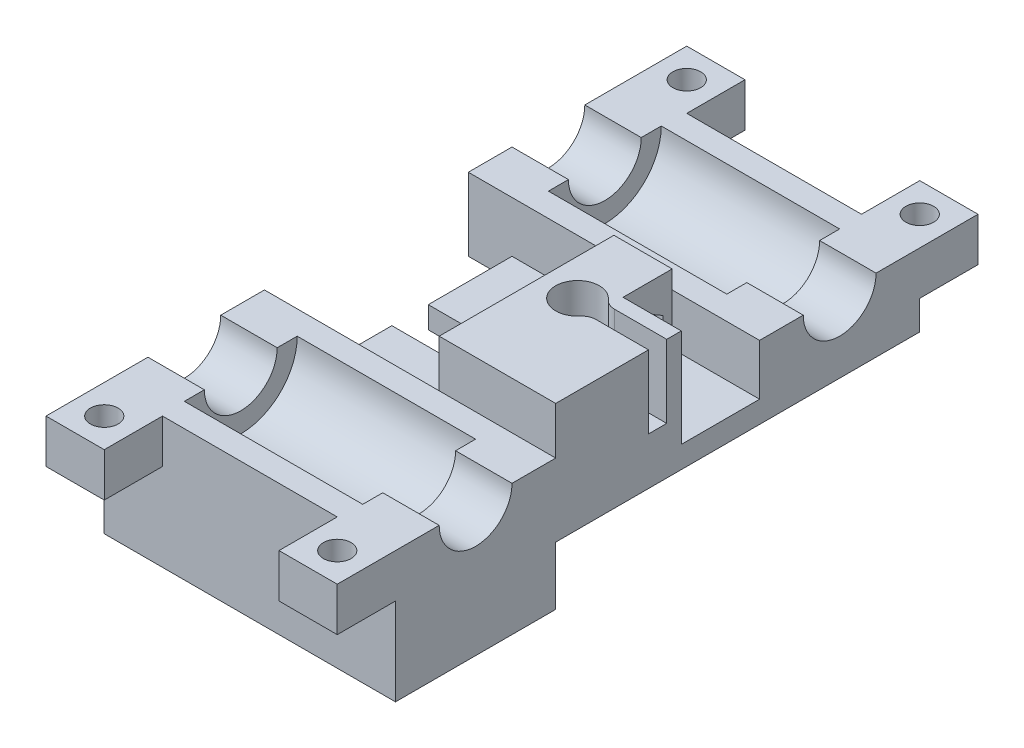
SolidWorks part; units mm, degrees
ref_plane "Front Plane" through (0, 0, 0) normal (0, 0, 1) x (1, 0, 0)
ref_plane "Top Plane" through (0, 0, 0) normal (0, 1, 0) x (1, 0, 0)
ref_plane "Right Plane" through (0, 0, 0) normal (1, 0, 0) x (0, 0, -1)
sketch "Sketch1" plane through (0, 0, 0) normal (0, 1, 0) x (1, 0, 0)
  line L1 (-20, 11) -> (20, 11)
  line L2 (-20, 11) -> (-20, -11)
  line L3 (-20, -11) -> (20, -11)
  line L4 (20, 11) -> (20, -11)
  line L5 (-20, 11) -> (20, -11) construction
  line L6 (-20, -11) -> (20, 11) construction
  point P0 (0, 0)
  dimension "D1" = 40
  dimension "D2" = 22
extrude "Boss-Extrude1" add sketch "Sketch1" along normal blind 11
sketch "Sketch2" plane through (0, 0, 0) normal (0, 1, 0) x (1, 0, 0)
  line L4 (20, -11) -> (20, 11)
  line L5 (-20, -11) -> (20, -11)
  line L6 (-20, 11) -> (-20, -11)
  line L7 (20, 11) -> (-20, 11)
  line L8 (20, -11) -> (20, 11)
  line L9 (-20, -11) -> (20, -11)
  line L10 (-20, 11) -> (-20, -11)
  line L11 (20, 11) -> (-20, 11)
  circle A0 centre (0, 0) radius 4
  dimension "D2" = 8
  dimension "D1" = 0
extrude "Boss-Extrude2" add sketch "Sketch2" against normal blind 7
sketch "Sketch3" plane through (0, 11, 0) normal (0, 1, 0) x (1, 0, 0)
  line L1 (12.25, -7.75) -> (-12.25, -7.75)
  line L2 (12.25, -7.75) -> (12.25, 7.75)
  line L3 (12.25, 7.75) -> (-12.25, 7.75)
  line L4 (-12.25, -7.75) -> (-12.25, 7.75)
  line L5 (12.25, -7.75) -> (-12.25, 7.75) construction
  line L6 (12.25, 7.75) -> (-12.25, -7.75) construction
  point P0 (0, 0)
  dimension "D1" = 15.5
  dimension "D2" = 24.5
extrude "Cut-Extrude1" cut sketch "Sketch3" against normal blind 7.75
fillet "Fillet1" radius 7.75 2 edges at (0, 3.25, 7.75) (0, 3.25, -7.75)
sketch "Sketch4" plane through (-12.25, 0, 0) normal (1, 0, 0) x (0, 0, -1)
  line L0 (7.75, 11) -> (-7.75, 11) construction
  circle A0 centre (0, 11) radius 5
  dimension "D1" = 10
extrude "Cut-Extrude2" cut sketch "Sketch4" against normal through all both and the other way through all
sketch "Sketch5" plane through (0, 11, 0) normal (0, 1, 0) x (1, 0, 0)
  line L1 (20, -11) -> (12, -11)
  line L2 (20, -11) -> (20, -19)
  line L3 (20, -19) -> (12, -19)
  line L4 (12, -11) -> (12, -19)
  circle A0 centre (16, -15) radius 1.9058
  dimension "D1" = 8
  dimension "D2" = 8
  dimension "D3" = 4
  dimension "D4" = 4
extrude "Boss-Extrude3" add sketch "Sketch5" against normal blind 6
sketch "Sketch6" plane through (0, 5, 0) normal (0, -1, 0) x (1, 0, 0)
  line L4 (20, 11) -> (20, 19)
  line L5 (20, 19) -> (12, 19)
  line L6 (12, 19) -> (12, 11)
  line L7 (12, 11) -> (20, 11)
  line L8 (20, 11) -> (20, 19)
  line L9 (20, 19) -> (12, 19)
  line L10 (12, 19) -> (12, 11)
  line L11 (12, 11) -> (20, 11)
  circle A0 centre (16, 15) radius 1.9058 construction
  circle A1 centre (16, 15) radius 1.9058
  circle A2 centre (16, 15) radius 3
  circle M6 centre (16, 15) radius 1.9058
  dimension "D2" = 6
  dimension "D1" = 0
extrude "Cut-Extrude3" cut sketch "Sketch6" against normal blind 3 contours A2 M6 region at (13.0849, 5, 15)
mirror "Mirror8" about plane through (0, 0, 0) normal (1, 0, 0) of "Cut-Extrude3", "Boss-Extrude3"
mirror "Mirror9" [suppressed] about plane through (0, 0, 0) normal (0, 0, 1)
chamfer "Chamfer2" [suppressed] distance 4 angle 45
ref_plane "Plane1" through (0, 0, -25) normal (0, 0, 1) x (1, 0, 0)
sketch "Sketch7" plane through (0, 0, -11) normal (0, 0, -1) x (-1, 0, 0)
  line L0 (-20, 11) -> (-20, -7) construction
  line L1 (-20, 1) -> (-4, 1)
  line L2 (-20, 1) -> (-20, 17.5)
  line L3 (-20, 17.5) -> (-4, 17.5)
  line L4 (-4, 1) -> (-4, 17.5)
  line L5 (-20, 11) -> (20, 11) construction
  dimension "D1" = 16
  dimension "D2" = 16.5
  dimension "D3" = 6.5
extrude "Boss-Extrude5" add sketch "Sketch7" along normal blind 28
mirror "Mirror14" about plane through (0, 0, -25) normal (0, 0, 1) of "Mirror8", "Cut-Extrude3", "Boss-Extrude3", "Cut-Extrude2", "Fillet1", "Cut-Extrude1", "Boss-Extrude2", "Boss-Extrude1"
sketch "Sketch9" plane through (4, 0, 0) normal (-1, 0, 0) x (0, 0, 1)
  line L0 (-39, 1) -> (-39, 11) construction
  line L1 (-11, 1) -> (-39, 1)
  line L2 (-11, 1) -> (-11, 4)
  line L3 (-11, 4) -> (-39, 4)
  line L4 (-39, 1) -> (-39, 4)
  dimension "D1" = 3
extrude "Boss-Extrude6" add sketch "Sketch9" along normal blind 18
sketch "Sketch10" plane through (0, 17.5, 0) normal (0, 1, 0) x (1, 0, 0)
  line L0 (-12.375, 25) -> (12.375, 25) construction
  line L1 (20, 39) -> (20, 11) construction
  line L3 (9, 23.75) -> (20, 23.75)
  line L4 (9, 23.75) -> (9, 26.25)
  line L5 (9, 26.25) -> (20, 26.25)
  line L6 (20, 23.75) -> (20, 26.25)
  circle A0 centre (9, 25) radius 3
  line M4 (20, 11) -> (20, 39)
  dimension "D3" = 6
  dimension "D1" = 0
  dimension "D2" = 11
  dimension "D4" = 2.5
  dimension "D5" = 1.25
extrude "Cut-Extrude4" cut sketch "Sketch10" against normal blind 10 contours L3 A0 L5 L4 | L5 A0 L3 L4 | A0 L3 L5 M4 region at (10.4565, 17.5, -25) region at (8.4952, 17.5, -25) region at (15.955, 17.5, -25)
sketch "Sketch11" plane through (0, 7.5, 0) normal (0, 1, 0) x (1, 0, 0)
  arc A0 (11.7272, 26.25) -> (11.7272, 23.75) centre (9, 25) ccw construction
  arc A1 (11.7272, 26.25) -> (11.7272, 23.75) centre (9, 25) ccw
  circle A2 centre (9, 25) radius 1.75
  dimension "D1" = 3.5
extrude "Cut-Extrude5" cut sketch "Sketch11" against normal through all both and the other way through all contours A2 region at (9, 7.5, -25)
sketch "Sketch12" plane through (4, 0, 0) normal (-1, 0, 0) x (0, 0, 1)
  line L1 (-39, 4) -> (-39, 11) construction
  circle A0 centre (-31, 11) radius 1.75
  dimension "D3" = 3.5
  dimension "D1" = 0
  dimension "D2" = 8
extrude "Cut-Extrude6" cut sketch "Sketch12" against normal through all both and the other way through all
sketch "Sketch15" plane through (20, 0, 0) normal (1, 0, 0) x (0, 0, -1)
  line L1 (32.6923, 13.6869) -> (29.5192, 13.809)
  line L2 (29.5192, 13.809) -> (27.8269, 11.1221)
  line L3 (27.8269, 11.1221) -> (29.3077, 8.3131)
  line L4 (29.3077, 8.3131) -> (32.4808, 8.191)
  line L5 (32.4808, 8.191) -> (34.1731, 10.8779)
  line L6 (34.1731, 10.8779) -> (32.6923, 13.6869)
  circle A0 centre (31, 11) radius 1.75 construction
  circle A1 centre (31, 11) radius 1.75
  circle A2 centre (31, 11) radius 2.75 construction
  dimension "D1" = 5.5
extrude "Cut-Extrude9" [suppressed] cut sketch "Sketch15" against normal blind 12 contours L1 L2 L3 L4 L5 L6
sketch "Sketch16" [suppressed] plane through (20, 0, 0) normal (1, 0, 0) x (0, 0, -1)
  line L1 (27, 11) -> (39, 11)
  line L2 (27, 11) -> (27, 17.5)
  line L3 (27, 17.5) -> (39, 17.5)
  line L4 (39, 11) -> (39, 17.5)
  circle A0 centre (31, 11) radius 1.75 construction
  circle A1 centre (31, 11) radius 1.75
  circle A2 centre (31, 11) radius 4
  dimension "D1" = 8
extrude "Cut-Extrude11" [suppressed] cut sketch "Sketch16" against normal blind 8
chamfer "Chamfer3" [suppressed] distance 2.5 angle 45
fillet "Fillet2" radius 2 2 edges at (11.7272, 12.5, -23.75) (11.7272, 12.5, -26.25)
sketch "Sketch17" plane through (0, 1, 0) normal (0, -1, 0) x (1, 0, 0)
  line L1 (12.1754, -25) -> (10.5877, -22.25)
  line L2 (10.5877, -22.25) -> (7.4123, -22.25)
  line L3 (7.4123, -22.25) -> (5.8246, -25)
  line L4 (5.8246, -25) -> (7.4123, -27.75)
  line L5 (7.4123, -27.75) -> (10.5877, -27.75)
  line L6 (10.5877, -27.75) -> (12.1754, -25)
  circle A0 centre (9, -25) radius 1.75 construction
  circle A1 centre (9, -25) radius 1.75
  circle A2 centre (9, -25) radius 2.75 construction
  dimension "D1" = 5.5
extrude "Cut-Extrude12" cut sketch "Sketch17" against normal blind 3
sketch "Sketch18" plane through (0, 4, 0) normal (0, 1, 0) x (1, 0, 0)
  line L0 (-14, 11) -> (-14, 39) construction
  line L1 (-14, 22.5) -> (4, 22.5)
  line L2 (-14, 22.5) -> (-14, 27.5)
  line L3 (-14, 27.5) -> (4, 27.5)
  line L4 (4, 22.5) -> (4, 27.5)
  line L5 (-12.375, 25) -> (12.375, 25) construction
  dimension "D1" = 2.5
  dimension "D2" = 5
  dimension "D3" = 18
extrude "Cut-Extrude13" cut sketch "Sketch18" against normal through all both and the other way through all
fillet "Fillet3" radius 2.5 2 edges at (4, 2.5, -27.5) (4, 2.5, -22.5)
sketch "Sketch19" plane through (0, 1, 0) normal (0, -1, 0) x (1, 0, 0)
  line L4 (20, -39) -> (-20, -39)
  line L5 (-20, -39) -> (-20, -61)
  line L6 (-20, -61) -> (20, -61)
  line L7 (-14, -22.5) -> (1.5, -22.5)
  line L8 (1.5, -27.5) -> (-14, -27.5)
  line L9 (-14, -27.5) -> (-14, -39)
  line L10 (-14, -39) -> (20, -39)
  line L11 (20, -39) -> (20, -11)
  line L12 (20, -11) -> (-14, -11)
  line L13 (-14, -11) -> (-14, -22.5)
  line L14 (-14, -22.5) -> (1.5, -22.5)
  line L15 (1.5, -27.5) -> (-14, -27.5)
  line L16 (-14, -27.5) -> (-14, -39)
  line L17 (-14, -39) -> (20, -39)
  line L18 (20, -39) -> (20, -11)
  line L19 (20, -11) -> (-14, -11)
  line L20 (-14, -11) -> (-14, -22.5)
  line L21 (20, -61) -> (20, -39)
  line L22 (20, -39) -> (-20, -39)
  line L23 (-20, -39) -> (-20, -61)
  line L24 (-20, -61) -> (20, -61)
  line L25 (20, -61) -> (20, -39)
  arc A2 (4, -25) -> (1.5, -22.5) centre (1.5, -25) ccw
  arc A3 (1.5, -27.5) -> (4, -25) centre (1.5, -25) ccw
  arc A4 (4, -25) -> (1.5, -22.5) centre (1.5, -25) ccw
  arc A5 (1.5, -27.5) -> (4, -25) centre (1.5, -25) ccw
  line M25 (-14, -39) -> (20, -39)
  dimension "D1" = 0
  dimension "D2" = 0
extrude "Cut-Extrude14" cut sketch "Sketch19" along normal through all contours L24 L25 L22 L23 M25 region at (0, 1, -50)
sketch "Sketch20" plane through (0, 17.5, 0) normal (0, 1, 0) x (1, 0, 0)
  line L1 (4, 39) -> (40.1637, 39)
  line L2 (4, 39) -> (4, 35)
  line L3 (4, 35) -> (40.1637, 35)
  line L4 (40.1637, 39) -> (40.1637, 35)
  dimension "D1" = 4
sketch "Sketch21" plane through (20, 0, 0) normal (1, 0, 0) x (0, 0, -1)
  line L1 (31, 14.1754) -> (28.25, 12.5877)
  line L2 (28.25, 12.5877) -> (28.25, 9.4123)
  line L3 (28.25, 9.4123) -> (31, 7.8246)
  line L4 (31, 7.8246) -> (33.75, 9.4123)
  line L5 (33.75, 9.4123) -> (33.75, 12.5877)
  line L6 (33.75, 12.5877) -> (31, 14.1754)
  circle A0 centre (31, 11) radius 1.75 construction
  circle A1 centre (31, 11) radius 1.75
  circle A2 centre (31, 11) radius 2.75 construction
  dimension "D1" = 5.5
extrude "Cut-Extrude15" cut sketch "Sketch21" against normal blind 10
extrude "Cut-Extrude16" cut sketch "Sketch20" against normal up to surface (13.5 mm away) up to face at (-3.5964, 4, -31.7036)
sketch "Sketch22" plane through (20, 0, 0) normal (1, 0, 0) x (0, 0, -1)
  line L0 (28.25, 12.5877) -> (28.25, 9.4123) construction
  line L1 (35, 17.5) -> (28.25, 17.5)
  line L2 (35, 17.5) -> (35, 4)
  line L3 (35, 4) -> (28.25, 4)
  line L4 (28.25, 17.5) -> (28.25, 4)
  line L5 (39, 4) -> (35, 4) construction
  dimension "D1" = 0
  dimension "D2" = 0
extrude "Cut-Extrude18" cut sketch "Sketch22" against normal blind 8
sketch "Sketch23" plane through (0, 0, 0) normal (0, -1, 0) x (1, 0, 0)
  circle A1 centre (0, 0) radius 4
  circle A2 centre (0, 0) radius 4
  dimension "D1" = 0
extrude "Boss-Extrude8" add sketch "Sketch23" along normal blind 1
